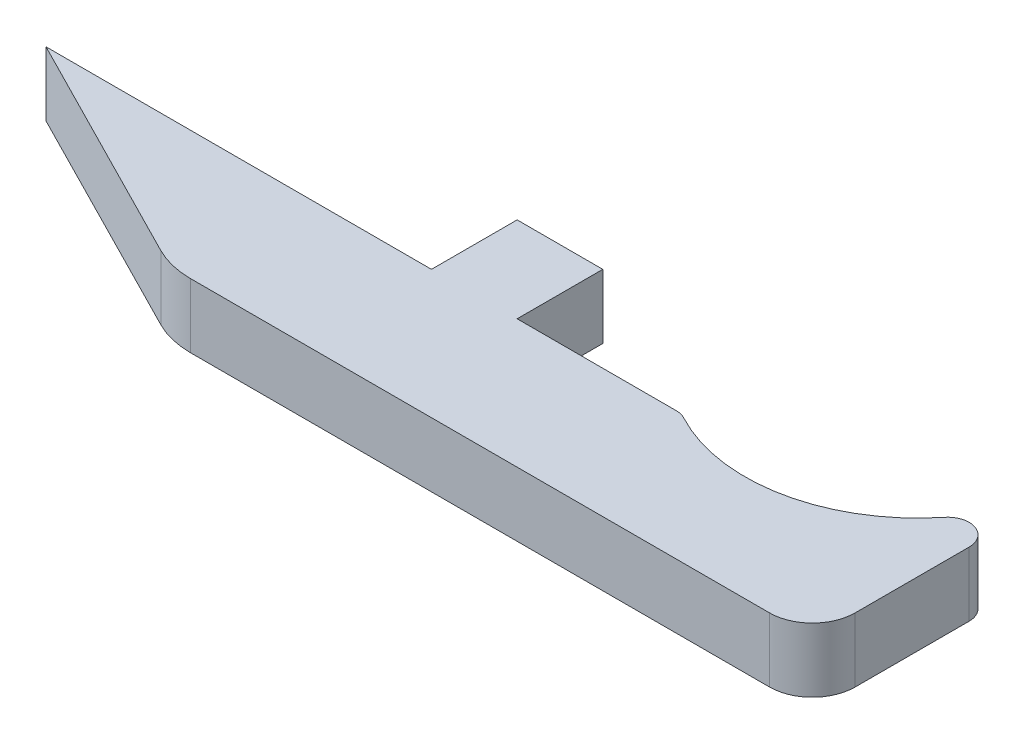
SolidWorks part; units mm, degrees
material "AISI 4130 Steel, annealed at 865C"
ref_plane "X-Y Datum" through (0, 0, 0) normal (0, 0, 1) x (1, 0, 0)
ref_plane "X-Z Datum" through (0, 0, 0) normal (0, 1, 0) x (1, 0, 0)
ref_plane "Y-Z Datum" through (0, 0, 0) normal (1, 0, 0) x (0, 0, -1)
sketch "Sketch1" plane through (0, 0, 0) normal (0, 1, 0) x (1, 0, 0)
  line L0 (59.0296, -10.8708) -> (59.0296, 14.5292) construction
  line L1 (59.0296, -9.296) -> (3.302, -9.296)
  line L2 (59.0296, -9.296) -> (59.0296, 1.8292)
  line L3 (24.2316, -18.821) -> (71.8566, -18.821)
  line L4 (71.8566, 1.8292) -> (71.8566, -18.821)
  line L5 (5.5225, -9.296) -> (24.2316, -18.821)
  line L7 (34.0975, -9.2833) -> (2.3475, -9.2833) construction
  line L8 (34.0975, -9.2833) -> (2.3475, -9.2833)
  circle A0 centre (59.0296, 1.8292) radius 12.827
  spline S0 degree 3 poles (59.0296, -10.8708) (33.6296, -10.8708) (33.6296, 14.5292) (59.0296, 14.5292) (84.4296, 14.5292) (84.4296, -10.8708) (59.0296, -10.8708) (33.6296, -10.8708) (33.6296, 14.5292) knots -0.5 0 0 0 0.5 0.5 0.5 1 1 1 1.5 1.5 1.5 weights 1 0.333333 0.333333 1 0.333333 0.333333 1 0.333333 0.333333 only from (59.0296, -10.8708) to (59.0296, -10.8708)
  spline S1 degree 3 poles (59.0296, -10.8708) (33.6296, -10.8708) (33.6296, 14.5292) (59.0296, 14.5292) (84.4296, 14.5292) (84.4296, -10.8708) (59.0296, -10.8708) (33.6296, -10.8708) (33.6296, 14.5292) knots -0.5 0 0 0 0.5 0.5 0.5 1 1 1 1.5 1.5 1.5 weights 1 0.333333 0.333333 1 0.333333 0.333333 1 0.333333 0.333333 only from (59.0296, -10.8708) to (59.0296, -10.8708) construction
  dimension "D3" = 25.654
  dimension "D5" = 9.525
  dimension "D1" = 55.7276
  dimension "D2" = 11.1252
  dimension "D4" = 3.175
  dimension "D6" = 47.625
extrude "Boss-Extrude1" add sketch "Sketch1" along normal blind 4.7625 contours L1 A0 region at (43.7069, 0, 13.6297)
fillet "Fillet1" radius 1.5875 2 edges at (52.6451, 2.3813, 9.296) (71.8566, 2.3813, -1.8292)
fillet "Fillet2" radius 6.35 1 edges at (24.2316, 2.3813, 18.821)
fillet "Fillet3" radius 3.175 1 edges at (71.8566, 2.3813, 18.821)
sketch "Sketch6" plane through (0, 0, 9.296) normal (0, 0, -1) x (-1, 0, 0)
  line L0 (-52.2351, 4.7625) -> (-5.5225, 4.7625) construction
  line L1 (-40.4475, 4.7625) -> (-34.0975, 4.7625)
  line L2 (-40.4475, 4.7625) -> (-40.4475, 0)
  line L3 (-40.4475, 0) -> (-34.0975, 0)
  line L4 (-34.0975, 4.7625) -> (-34.0975, 0)
  line L5 (-52.2351, 0) -> (-5.5225, 0) construction
  line L6 (-5.5225, 4.7625) -> (-5.5225, 0) construction
  dimension "D1" = 6.35
  dimension "D2" = 28.575
extrude "Boss-Extrude2" add sketch "Sketch6" along normal blind 6.35
